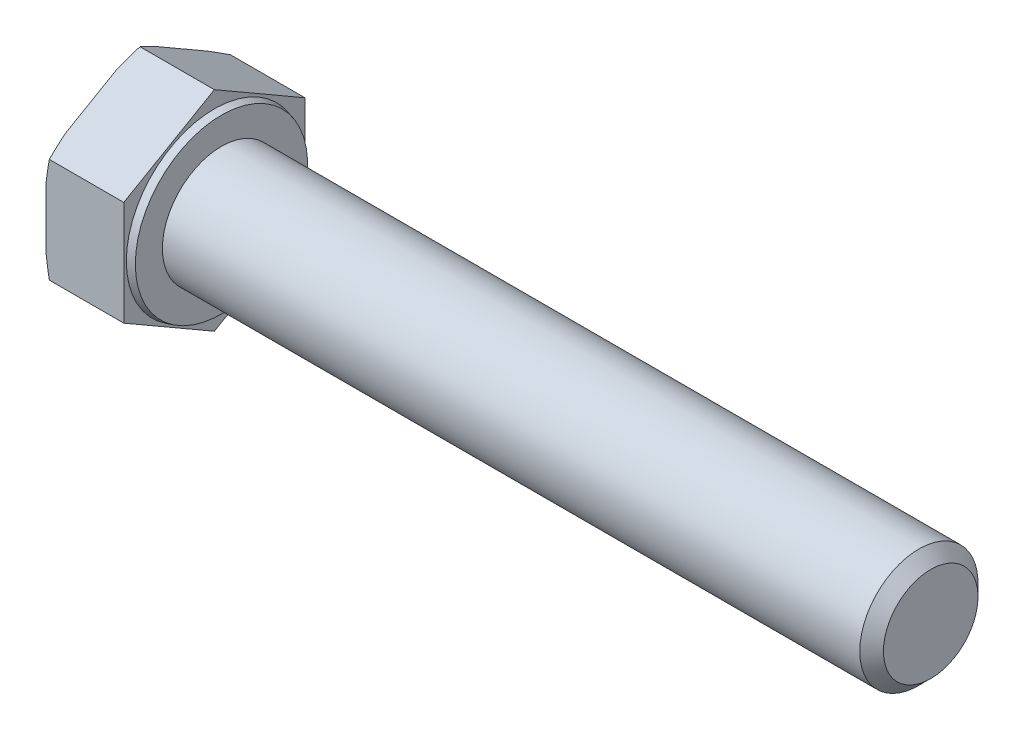
SolidWorks part; units mm, degrees
material "AISI 1020"
ref_plane "Спереди" through (0, 0, 0) normal (0, 0, 1) x (1, 0, 0)
ref_plane "Сверху" through (0, 0, 0) normal (0, 1, 0) x (1, 0, 0)
ref_plane "Справа" through (0, 0, 0) normal (1, 0, 0) x (0, 0, -1)
sketch "Эскиз1" plane through (0, 0, 0) normal (0, 0, 1) x (1, 0, 0)
  line L0 (-1000, 0) -> (49000, 0) construction
  line L1 (-6.58, 0) -> (-6.58, 8.85)
  line L2 (-6.58, 8.85) -> (0, 8.85)
  line L3 (0, 8.85) -> (0, 7.449)
  line L4 (0.6, 5) -> (60.6, 5)
  line L5 (60.6, 5) -> (60.6, 0)
  line L6 (-6.58, 0) -> (60.6, 0)
  line L7 (0, 7.449) -> (0.6, 7.2882)
  line L8 (0.6, 7.2882) -> (0.6, 5)
  line L9 (0.5, 0) -> (0.5, 7.315) construction
  dimension "D1" = 60
  dimension "D5" = 17.7
  dimension "D2" = 0.6
  dimension "D3" = 6.58
  dimension "D4" = 0.1
  dimension "D6" = 14.63
  dimension "D7" = 75
revolve "Повернуть1" add sketch "Эскиз1" angle 360 about L0
sketch "Эскиз2" plane through (-6.58, 0, 0) normal (-1, 0, 0) x (0, 0, 1)
  line L1 (0, -8.85) -> (7.6643, -4.425)
  line L2 (7.6643, -4.425) -> (7.6643, 4.425)
  line L3 (7.6643, 4.425) -> (0, 8.85)
  line L4 (0, 8.85) -> (-7.6643, 4.425)
  line L5 (-7.6643, 4.425) -> (-7.6643, -4.425)
  line L6 (-7.6643, -4.425) -> (0, -8.85)
  circle A0 centre (0, 0) radius 7.6643 construction
  circle A1 centre (0, 0) radius 8.85 construction
extrude "Вырез-Вытянуть1" cut sketch "Эскиз2" against normal through all flip side to cut
sketch "Эскиз4" plane through (0, 0, 0) normal (0, 0, 1) x (1, 0, 0)
  line L0 (-1000, 0) -> (49000, 0) construction
  line L1 (-6.58, 8.075) -> (-6.2979, 8.85)
  line L2 (-6.2979, 8.85) -> (-6.58, 8.85)
  line L3 (-6.58, 8.85) -> (-6.58, 8.075)
  line L4 (-6.58, 4.425) -> (-6.58, 8.85) construction
  line L6 (0, 8.85) -> (-6.58, 8.85) construction
  dimension "D1" = 20
  dimension "D2" = 16.15
revolve "Вырез-Повернуть1" cut sketch "Эскиз4" angle 360 about L0
chamfer "Фаска1" distance 1 angle 45 1 edges at (60.6, 0, 5)
equation "\"l\"= 60'длина болта"
equation "\"_d\"= 10'диаметр болта"
equation "\"b\"= 20'длина резьбы"
equation "\"k\"= 6.58'толщина шляпки"
equation "\"e\"= 17.7'диаметр головки описанный"
equation "\"S\"= 17'размер под ключ"
equation "\"_d@Эскиз1\"=\"_d\""
equation "\"dw\"= 14.63"
equation "\"da\"= 9.78"
equation "\"с\"= 0.6"
equation "\"D1@Эскиз1\"=\"l\""
equation "\"D5@Эскиз1\"=\"e\""
equation "\"D2@Эскиз1\"=\"с\""
equation "\"D3@Эскиз1\"=\"k\""
equation "\"D2@Эскиз4\"=\"S\"*0.95"
equation "\"D1@Фаска1\"=\"_d\"/10"
equation "\"D6@Эскиз1\"=\"dw\""
